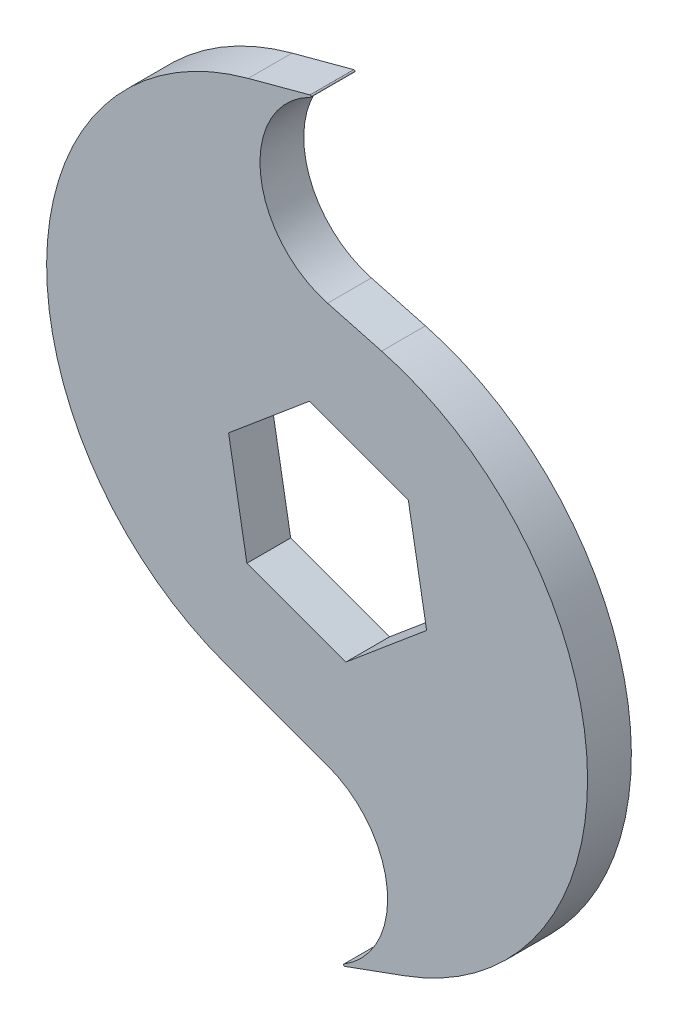
SolidWorks part; units mm, degrees
ref_plane "Front Plane" through (0, 0, 0) normal (0, 0, 1) x (1, 0, 0)
ref_plane "Top Plane" through (0, 0, 0) normal (0, 1, 0) x (1, 0, 0)
ref_plane "Right Plane" through (0, 0, 0) normal (1, 0, 0) x (0, 0, -1)
sketch "Sketch1" plane through (0, 0, 0) normal (0, 0, 1) x (1, 0, 0)
  line L0 (0, 52.07) -> (-11.0405, 49.1117)
  line L1 (0, 52.07) -> (0, 0) construction
  line L2 (0, -52.07) -> (10.7407, -48.1607)
  line L3 (0, 0) -> (0, -52.07) construction
  line L5 (-2.5465, 14.4419) -> (-13.7803, 5.0156)
  line L6 (-13.7803, 5.0156) -> (-11.2338, -9.4263)
  line L7 (-11.2338, -9.4263) -> (2.5465, -14.4419)
  line L8 (2.5465, -14.4419) -> (13.7803, -5.0156)
  line L9 (13.7803, -5.0156) -> (11.2338, 9.4263)
  line L10 (11.2338, 9.4263) -> (-2.5465, 14.4419)
  line L11 (0, 27.5355) -> (7.5237, 25.5195)
  line L12 (0, -28.2018) -> (-14.1906, -23.0368)
  circle A0 centre (0, 0) radius 52.07 construction
  arc A1 (0, 52.07) -> (0, 27.5355) centre (3.287, 39.8027) ccw
  arc A3 (0, -52.07) -> (0, -28.2018) centre (-4.3437, -40.1359) ccw
  arc A4 (10.7407, -48.1607) -> (7.5237, 25.5195) centre (-2.4834, -11.8278) ccw
  arc A5 (-11.0405, 49.1117) -> (-14.1906, -23.0368) centre (-1.2414, 12.5408) ccw
  circle A6 centre (0, 0) radius 12.7 construction
  dimension "D4" = 70
  dimension "D5" = 25.4
  dimension "D1" = 104.14
  dimension "D6" = 12.7
  dimension "D2" = 11.43
  dimension "D3" = 75
  dimension "D7" = 10
extrude "Boss-Extrude1" add sketch "Sketch1" along normal mid plane 6.096
fillet "Fillet1" radius 0.127 2 edges at (0, 52.07, 0) (0, -52.07, 0)
